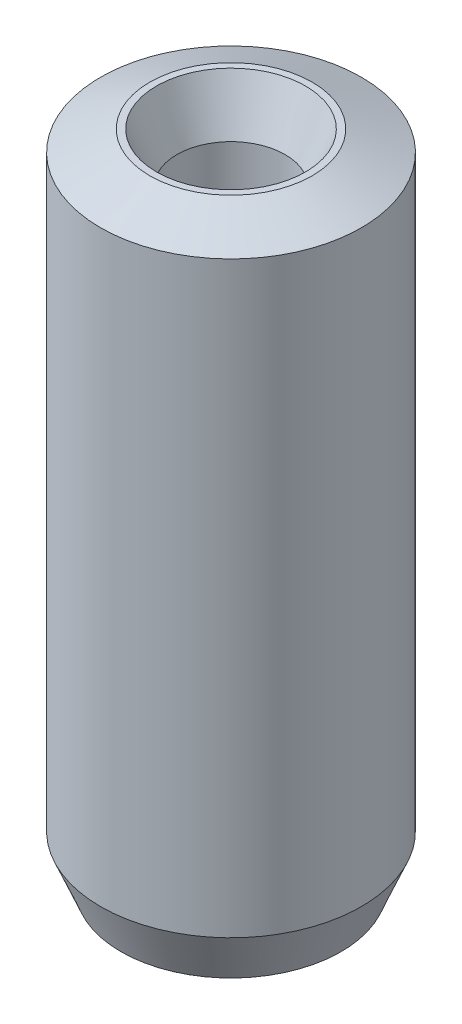
SolidWorks part; units mm, degrees
ref_plane "Front Plane" through (0, 0, 0) normal (0, 0, 1) x (1, 0, 0)
ref_plane "Top Plane" through (0, 0, 0) normal (0, 1, 0) x (1, 0, 0)
ref_plane "Right Plane" through (0, 0, 0) normal (1, 0, 0) x (0, 0, -1)
sketch "Sketch1" plane through (0, 0, 0) normal (0, 1, 0) x (1, 0, 0)
  circle A0 centre (0, 0) radius 15
  dimension "SLEEVE_OD" = 30
extrude "Boss-Extrude1" add sketch "Sketch1" along normal blind 75.6177
sketch "Sketch2" plane through (0, 0, 0) normal (0, 1, 0) x (1, 0, 0)
  circle A0 centre (0, 0) radius 6.2281
  dimension "BORE_D" = 12.4562
extrude "Cut-Extrude1" cut sketch "Sketch2" along normal through all
chamfer "Chamfer1" distance 2.3409 angle 67.546 4 edges at (0, 75.6177, 6.2281) (0, 0, 6.2281) (0, 0, 15) (0, 75.6177, 15) first distance on face at (0, 75.6177, 6.2281) first distance on face at (0, 0, 6.2281) first distance on face at (0, 75.6177, 15)
